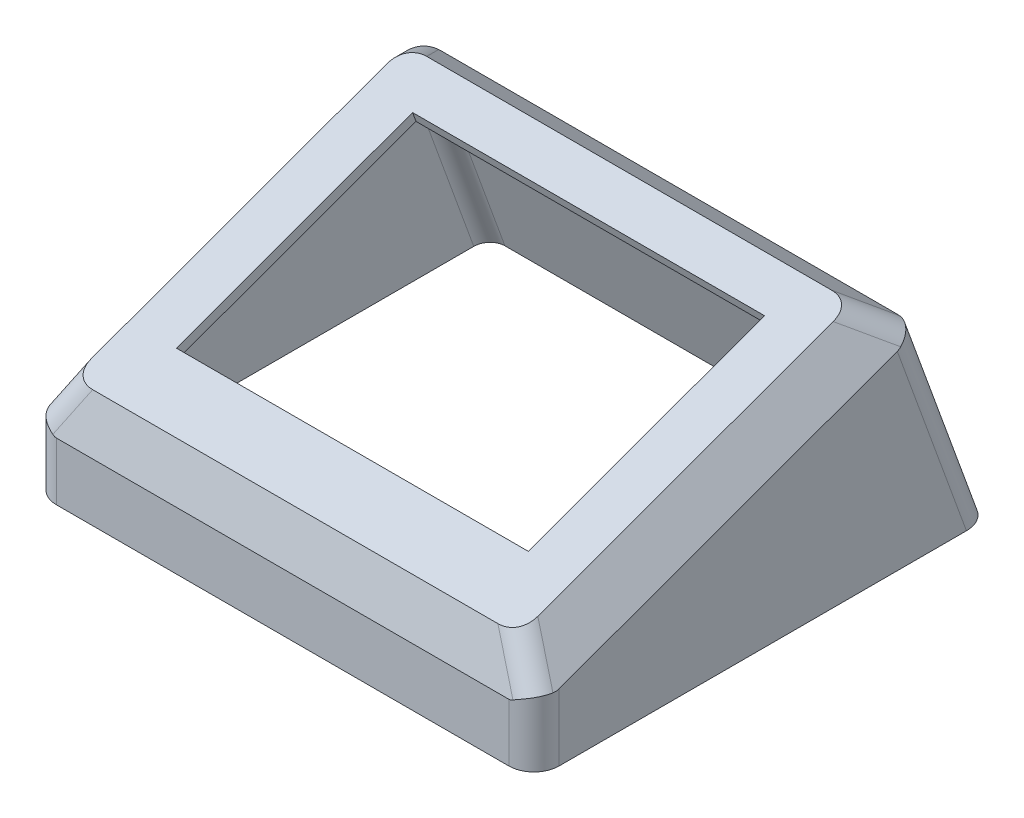
SolidWorks part; units mm, degrees
ref_plane "Front Plane" through (0, 0, 0) normal (0, 0, 1) x (1, 0, 0)
ref_plane "Top Plane" through (0, 0, 0) normal (0, 1, 0) x (1, 0, 0)
ref_plane "Right Plane" through (0, 0, 0) normal (1, 0, 0) x (0, 0, -1)
sketch "Sketch2" plane through (0, 0, 0) normal (1, 0, 0) x (0, 0, -1)
  line L0 (-74.2357, 0) -> (-74.2357, 20)
  line L1 (55, 0) -> (-55, 0) construction
  line L2 (-74.2357, 20) -> (0, 47.0196)
  line L3 (0, 55) -> (0, -55) construction
  line L4 (0, 47.0196) -> (17.1137, 0)
  line L5 (17.1137, 0) -> (-74.2357, 0)
  dimension "D1" = 79
  dimension "D2" = 20
  dimension "D3" = 110
extrude "Boss-Extrude1" add sketch "Sketch2" along normal blind 50 and the other way blind 50
chamfer "Chamfer3" distance 8 angle 35 3 edges at (50, 33.5098, 37.1179) (0, 47.0196, 0) (-50, 33.5098, 37.1179) first distance on face at (50, 16.7549, 32.8394) first distance on face at (0, 23.5098, -8.5569) first distance on face at (-50, 16.7549, 32.8394)
chamfer "Chamfer4" distance 8.5 angle 15 1 edges at (0, 20, 74.2357) first distance on face at (0, 10.4955, 74.2357)
fillet "Fillet7" radius 5 8 edges at (-50, 19.751, -9.9249) (50, 19.751, -9.9249) (-50, 5.7433, 74.2357) (50, 5.7433, 74.2357) (-47.1992, 42.3029, 1.2638) (-47.1948, 16.2093, 72.9739) (47.1992, 42.3029, 1.2638) (47.1948, 16.2093, 72.9739)
shell "Shell1" thickness 2 removed face at (0, 0, 28.6246)
sketch "Sketch3" plane through (0, 41.5193, 15.1118) normal (0, 0.9397, 0.342) x (1, 0, 0)
  line L0 (0, -55) -> (0, 55) construction
  line L1 (35, -48.157) -> (-35, -48.157)
  line L2 (35, -48.157) -> (35, 1.843)
  line L3 (35, 1.843) -> (-35, 1.843)
  line L4 (-35, -48.157) -> (-35, 1.843)
  line L5 (35, -48.157) -> (-35, 1.843) construction
  line L6 (35, 1.843) -> (-35, -48.157) construction
  point P0 (0, -23.157)
  dimension "D1" = 70
  dimension "D2" = 50
extrude "Cut-Extrude1" cut sketch "Sketch3" against normal up to surface (2 mm away) up to face at (0, 31.1317, 37.8039)
sketch "Sketch4" plane through (0, 5.5002, -15.1118) normal (0, 0.342, -0.9397) x (-1, 0, 0)
  line L0 (-4.7507, 27.424) -> (-11.0291, 27.424) construction
  line L1 (-4.7507, 25.794) -> (-11.0291, 25.794)
  line L2 (-4.7507, 29.054) -> (-11.0291, 29.054)
  line L8 (-1.72, 27.732) -> (8.28, 27.732)
  line L9 (-1.72, 27.732) -> (-1.72, 24.237)
  line L10 (-1.72, 24.237) -> (8.28, 24.237)
  line L11 (8.28, 27.732) -> (8.28, 24.237)
  line L12 (-4.7704, 27.124) -> (-11.0271, 27.124) construction
  arc A0 (-4.7507, 25.794) -> (-4.7507, 29.054) centre (-4.7507, 27.424) ccw
  arc A1 (-11.0291, 29.054) -> (-11.0291, 25.794) centre (-11.0291, 27.424) ccw
  point P2 (-7.8899, 27.424)
  point P7 (-7.8938, 25.537)
  point P8 (-7.8899, 25.8376)
  dimension "D1" = 10
  dimension "D2" = 3.4
  dimension "D3" = 0.3
extrude "Cut-Extrude2" cut sketch "Sketch4" against normal up to surface (2 mm away) up to face at (0, 19.1127, -8.0289)
